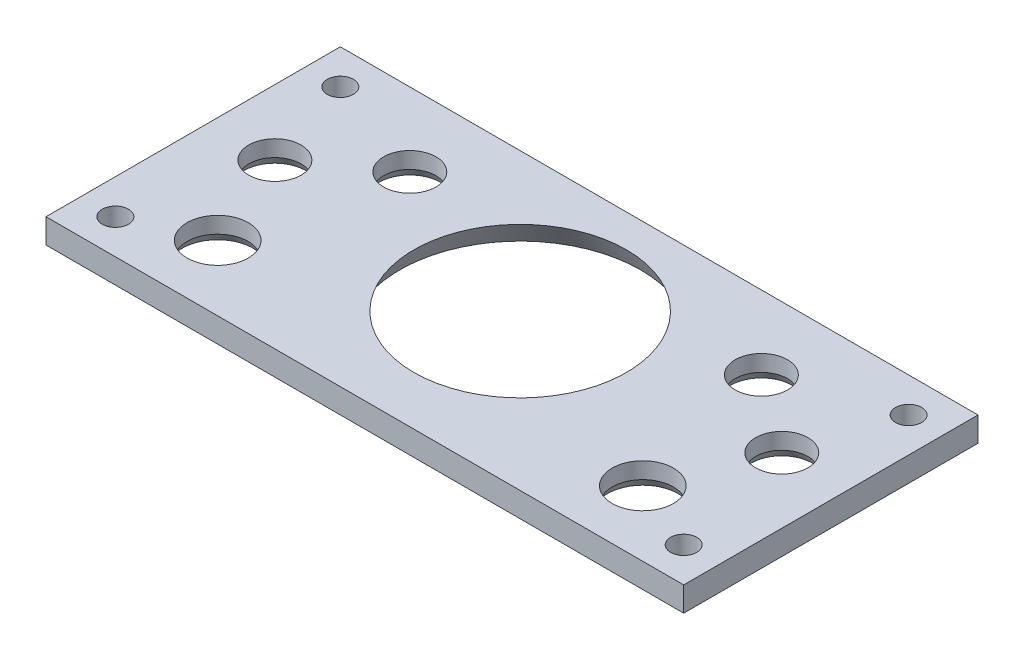
SolidWorks part; units mm, degrees
ref_plane "Спереди" through (0, 0, 0) normal (0, 0, 1) x (1, 0, 0)
ref_plane "Сверху" through (0, 0, 0) normal (0, 1, 0) x (1, 0, 0)
ref_plane "Справа" through (0, 0, 0) normal (1, 0, 0) x (0, 0, -1)
sketch "Sketch1" plane through (0, 0, 0) normal (0, 1, 0) x (1, 0, 0)
  line L0 (-31, 18) -> (-31, -18) construction
  line L1 (39, -18) -> (-39, -18)
  line L2 (39, -18) -> (39, 18)
  line L3 (39, 18) -> (-39, 18)
  line L4 (-39, -18) -> (-39, 18)
  line L5 (39, -18) -> (-39, 18) construction
  line L6 (39, 18) -> (-39, -18) construction
  line L7 (31, 18) -> (31, -18) construction
  line L8 (-21.5, 18) -> (-21.5, -18) construction
  line L9 (21.5, 18) -> (21.5, -18) construction
  line L12 (-31, 2) -> (31, 2) construction
  line L13 (26, -10) -> (-26, -10) construction
  line L14 (0, 18) -> (0, -18) construction
  line L16 (-31, 2) -> (-39, 2) construction
  line L17 (31, 2) -> (39, 2) construction
  circle A0 centre (0, 1) radius 13
  circle A1 centre (-31, 2) radius 3.2
  circle A2 centre (-26, -10) radius 3.75
  circle A3 centre (31, 2) radius 3.2
  circle A4 centre (26, -10) radius 3.75
  circle A5 centre (0, 1) radius 19 construction
  circle A6 centre (21.5, 9) radius 3.2
  circle A7 centre (-21.5, 9) radius 3.2
  point P0 (0, 0)
  point P33 (21, 10.2503)
  point P34 (-21, 10.2503)
  point P35 (22, 8.939)
  dimension "D3" = 26
  dimension "D6" = 6.4
  dimension "D10" = 7.5
  dimension "D11" = 6
  dimension "D13" = 7
  dimension "D12" = 7
  dimension "D1" = 78
  dimension "D2" = 36
  dimension "D4" = 8
  dimension "D5" = 8
  dimension "D7" = 2
  dimension "D8" = 10
  dimension "D9" = 1
  dimension "D14" = 13
  dimension "D15" = 13
  dimension "D17" = 43
  dimension "D18" = 21.5
extrude "Boss-Extrude1" add sketch "Sketch1" along normal blind 3
chamfer "Chamfer1" distance 3 angle 30 1 edges at (0, 0, 12) first distance on face at (0, 3, 12)
chamfer "Chamfer2" distance 1 angle 30 6 edges at (31, 0, 1.2) (26, 0, 13.75) (-31, 0, 1.2) (-26, 0, 13.75) (-21.5, 0, -5.8) (21.5, 0, -5.8) first distance on face at (31, 3, 1.2) first distance on face at (26, 3, 13.75) first distance on face at (-31, 3, 1.2) first distance on face at (-26, 3, 13.75) first distance on face at (-21.5, 3, -5.8) first distance on face at (21.5, 3, -5.8)
sketch "Sketch2" plane through (0, 3, 0) normal (0, 1, 0) x (1, 0, 0)
  line L0 (0, 18) -> (0, -18) construction
  line L1 (39, 18) -> (-39, 18) construction
  line L2 (-39, -18) -> (39, -18) construction
  line L3 (-39, -18) -> (-34.7574, -13.7574) construction
  line L4 (34.7574, 13.7574) -> (-34.7574, 13.7574) construction
  line L5 (34.7574, 13.7574) -> (34.7574, -13.7574) construction
  line L6 (34.7574, -13.7574) -> (-34.7574, -13.7574) construction
  line L7 (-34.7574, 13.7574) -> (-34.7574, -13.7574) construction
  line L8 (34.7574, 13.7574) -> (-34.7574, -13.7574) construction
  line L9 (34.7574, -13.7574) -> (-34.7574, 13.7574) construction
  line L10 (-39, 18) -> (-39, -18) construction
  circle A0 centre (-34.7574, -13.7574) radius 1.6
  circle A1 centre (-34.7574, 13.7574) radius 1.6
  circle A2 centre (34.7574, 13.7574) radius 1.6
  circle A3 centre (34.7574, -13.7574) radius 1.6
  point P6 (0, 0)
  dimension "D3" = 3.2
  dimension "D1" = 45
  dimension "D2" = 6
extrude "Cut-Extrude1" cut sketch "Sketch2" against normal through all
sketch "Sketch6" plane through (0, 3, 0) normal (0, 1, 0) x (1, 0, 0)
  circle A0 centre (-34.7574, -13.7574) radius 3.5
  dimension "D1" = 7
sketch "Sketch7" plane through (0, 3, 0) normal (0, 1, 0) x (1, 0, 0)
  circle A0 centre (0, 1) radius 18.5
  circle A1 centre (0, 1) radius 13 construction
  dimension "D1" = 5.5
sketch "Sketch8" plane through (0, 3, 0) normal (0, 1, 0) x (1, 0, 0)
  circle A0 centre (-31, 2) radius 4.5
  circle A1 centre (-21.5, 9) radius 4.5
  dimension "D1" = 9
sketch "Sketch9" plane through (0, 3, 0) normal (0, 1, 0) x (1, 0, 0)
  circle A0 centre (-26, -10) radius 5
  dimension "D1" = 10
